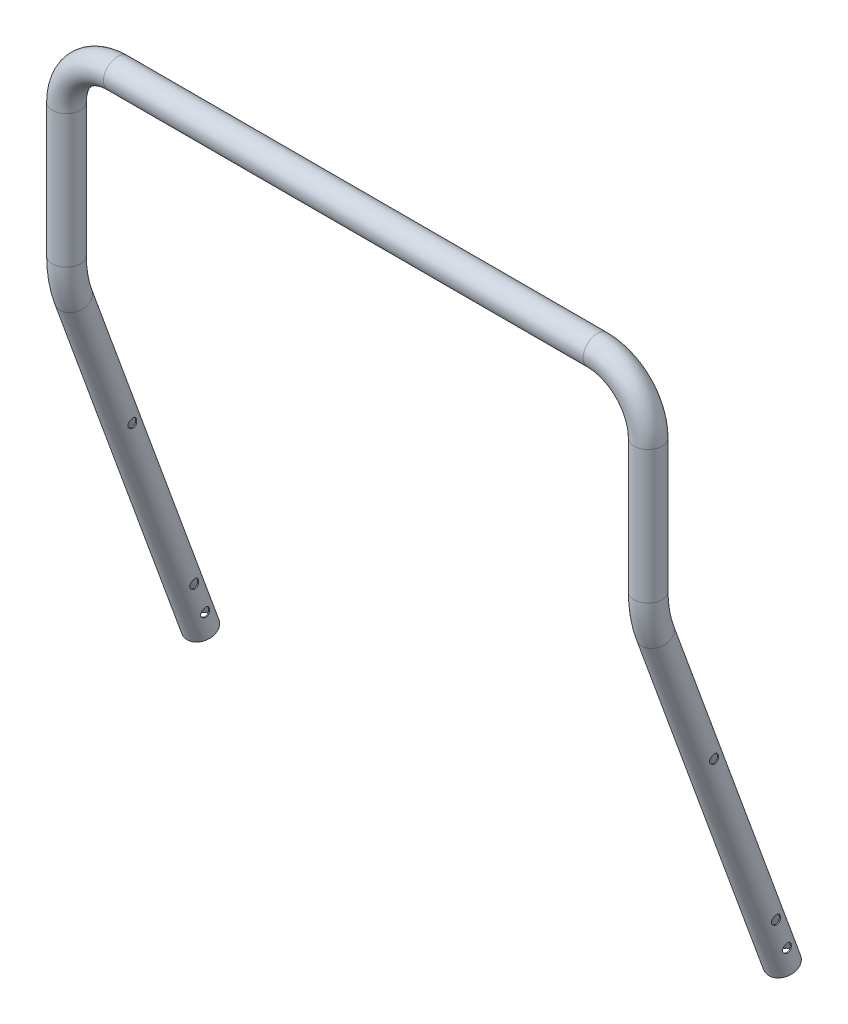
SolidWorks part; units mm, degrees
ref_plane "Front Plane" through (0, 0, 0) normal (0, 0, 1) x (1, 0, 0)
ref_plane "Top Plane" through (0, 0, 0) normal (0, 1, 0) x (1, 0, 0)
ref_plane "Right Plane" through (0, 0, 0) normal (1, 0, 0) x (0, 0, -1)
sketch "Sketch8" plane through (0, 0, 0) normal (0, 0, 1) x (1, 0, 0)
  line L0 (-188, 0) -> (188, 0)
  line L1 (-228, -40) -> (-228, -100)
  line L2 (228, -40) -> (228, -100)
  arc A0 (228, -40) -> (188, 0) centre (188, -40) ccw
  arc A1 (-188, 0) -> (-228, -40) centre (-188, -40) ccw
  point P4 (0, 0)
  point P9 (228, 0)
  point P12 (-228, 0)
  dimension "D2" = 40
  dimension "450" = 456
  dimension "D3" = 60
  dimension "D4" = 60
ref_plane "Plane3" through (228, -100, 0) normal (0, -1, 0) x (-1, 0, 0)
sketch "Sketch9" plane through (228, -100, 0) normal (0, -1, 0) x (-1, 0, 0)
  circle A0 centre (0, 0) radius 11
  circle A1 centre (0, 0) radius 10.2
  dimension "D1" = 0.8
ref_plane "Plane5" through (228, 0, 0) normal (1, 0, 0) x (0, 0, -1)
sketch "Sketch13" plane through (228, 0, 0) normal (1, 0, 0) x (0, 0, -1)
  line L0 (0, -100) -> (0, -144.2597)
  line L1 (-11, -100) -> (11, -100) construction
  line L2 (5.4277, -175.0415) -> (104.9678, -448.5257)
  arc A0 (5.4277, -175.0415) -> (0, -144.2597) centre (90, -144.2597) cw
  dimension "D1" = 90
  dimension "D2" = 160
sweep "Sweep2" add profiles "Sketch9" path "Sketch8"
sweep "Sweep3" add profiles "Sketch9<2>" path "Sketch13"
sketch "Sketch9<2>" plane through (228, -100, 0) normal (0, -1, 0) x (-1, 0, 0) same geometry as "Sketch9"
mirror "Mirror1" about plane through (0, 0, 0) normal (1, 0, 0) of "Sweep3"
sketch "Sketch14" plane through (228, 0, 0) normal (1, 0, 0) x (0, 0, -1)
  line L0 (104.9678, -448.5257) -> (5.4277, -175.0415) construction
  line L1 (94.6311, -452.2879) -> (115.3044, -444.7635) construction
  line L2 (15.7643, -171.2793) -> (-4.909, -178.8037) construction
  circle A0 centre (41.0559, -272.9293) radius 3.5
  circle A1 centre (89.6228, -406.3657) radius 3.5
  circle A3 centre (98.1733, -429.858) radius 3.5
  circle A4 centre (0, 0) radius 10.2 construction
  dimension "D1" = 142
  dimension "D2" = 25
  dimension "D3" = 276
extrude "Cut-Extrude1" cut sketch "Sketch14" against normal up to next and the other way up to next
mirror "Mirror2" about plane through (0, 0, 0) normal (1, 0, 0) of "Cut-Extrude1"
